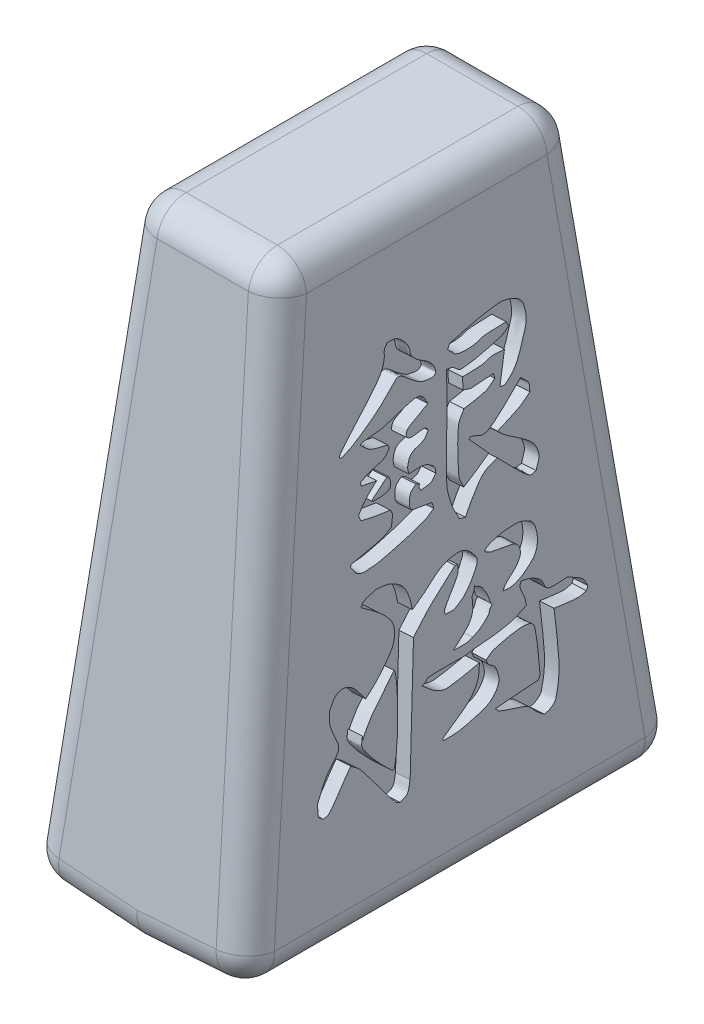
SolidWorks part; units mm, degrees
ref_plane "Płaszczyzna przednia" through (0, 0, 0) normal (0, 0, 1) x (1, 0, 0)
ref_plane "Płaszczyzna górna" through (0, 0, 0) normal (0, 1, 0) x (1, 0, 0)
ref_plane "Płaszczyzna prawa" through (0, 0, 0) normal (1, 0, 0) x (0, 0, -1)
sketch "Szkic1" plane through (0, 0, 0) normal (0, 0, 1) x (1, 0, 0)
  line L0 (0, 0) -> (0, 40)
  line L1 (3.1225, 40) -> (-3.1225, 40)
  line L2 (-5.1185, 38.1262) -> (-7.3738, 2.4704)
  line L3 (-5.504, 0.3481) -> (0, 0)
  line L4 (5.504, 0.3481) -> (0, 0)
  line L5 (5.1185, 38.1262) -> (7.3738, 2.4704)
  arc A0 (-3.1225, 40) -> (-5.1185, 38.1262) centre (-3.1225, 38) ccw
  arc A1 (-7.3738, 2.4704) -> (-5.504, 0.3481) centre (-5.3777, 2.3441) ccw
  arc A2 (7.3738, 2.4704) -> (5.504, 0.3481) centre (5.3777, 2.3441) cw
  arc A3 (3.1225, 40) -> (5.1185, 38.1262) centre (3.1225, 38) cw
  point P7 (-5, 40)
  point P10 (-7.5, 0.4744)
  point P17 (7.5, 0.4744)
  point P18 (5, 40)
  dimension "D5" = 2
  dimension "D1" = 40
  dimension "D2" = 90
  dimension "D3" = 5
  dimension "D4" = 7.5
extrude "Dodanie-wyciągnięcie1" add sketch "Szkic1" along normal blind 30 contours L2 A1 L3 L0 L1 A0 | A3 L1 L0 L4 A2 L5 region at (-3.1441, 18.7866, 0) region at (3.1441, 18.7866, 0)
ref_plane "Płaszczyzna1" through (5.1225, 0, 0) normal (1, 0, 0) x (0, 0, -1)
ref_plane "Płaszczyzna2" through (15.1225, 0, 0) normal (1, 0, 0) x (0, 0, -1)
sketch "Szkic7" plane through (15.1225, 0, 0) normal (1, 0, 0) x (0, 0, -1)
  line L0 (-25, 40) -> (-5, 40)
  line L1 (-30, 40) -> (0, 40) construction
  line L2 (-5, 40) -> (0, 0)
  line L3 (0, 0) -> (-30, 0)
  line L4 (-30, 0) -> (0, 0) construction
  line L5 (-15, 0) -> (-15, 40)
  line L6 (-25, 40) -> (-30, 0)
  line L8 (0, 0) -> (-30, 0)
  line L9 (0, 0) -> (0, 40)
  line L10 (0, 40) -> (-30, 40)
  line L11 (-30, 0) -> (-30, 40)
  dimension "D1" = 10
  dimension "D2" = 15
  dimension "D3" = 40
extrude "Wytnij-wyciągnięcie11" cut sketch "Szkic7" against normal through all and the other way through all contours L11 L6 L10 | L9 L10 L2 region at (15.1225, 26.6667, 28.3333) region at (15.1225, 26.6667, 1.6667)
fillet "Zaokrąglenie2" radius 2 18 edges at (0, 40, 5) (-4.4914, 39.4582, 4.9323) (-6.2461, 20.2983, 2.5373) (-6.8784, 1.022, 0.1278) (-2.752, 0.1741, 0.0218) (2.752, 0.1741, 0.0218) (6.8784, 1.022, 0.1278) (6.2461, 20.2983, 2.5373) (4.4914, 39.4582, 4.9323) (4.4914, 39.4582, 25.0677) (6.2461, 20.2983, 27.4627) (6.8784, 1.022, 29.8722) (2.752, 0.1741, 29.9782) (-2.752, 0.1741, 29.9782) (-6.8784, 1.022, 29.8722) (-6.2461, 20.2983, 27.4627) (-4.4914, 39.4582, 25.0677) (0, 40, 25)
sketch "Szkic8" plane through (7.5, 0.4744, 0) normal (0.998, 0.0631, 0) x (0, 0, -1)
  line L0 (200, 714.5) -> (1000, 714.5) construction
  line L1 (-16.3932, 23.4436) -> (-16.6352, 23.5536)
  line L2 (-17.0092, 22.2336) -> (-15.6452, 22.0136)
  line L3 (-15.6452, 22.0136) -> (-15.5352, 21.6176)
  line L4 (-21.2772, 21.0236) -> (-21.2112, 21.1556)
  line L5 (-19.2312, 25.0056) -> (-20.2872, 25.2036)
  line L6 (-20.2872, 25.2036) -> (-20.3092, 25.4236)
  line L7 (-18.2852, 26.4136) -> (-18.3732, 26.6556)
  line L8 (-18.5492, 24.8736) -> (-18.4392, 24.8516)
  line L9 (-19.6492, 24.0376) -> (-18.5492, 24.8736)
  line L10 (-10.7172, 26.2816) -> (-10.2772, 28.2396)
  line L11 (-13.1592, 28.0416) -> (-13.1812, 27.2936)
  line L12 (-11.0912, 27.2276) -> (-11.0252, 26.9196)
  line L13 (-11.6852, 22.9376) -> (-12.9612, 24.3456)
  line L14 (-13.4672, 20.0996) -> (-13.8632, 20.2096)
  line L15 (-9.9252, 29.3836) -> (-10.0572, 29.7136)
  line L16 (-14.1272, 17.7016) -> (-14.3252, 17.7456)
  line L17 (-17.3392, 15.0616) -> (-18.0652, 7.2076)
  line L18 (-23.9612, 7.8016) -> (-24.2912, 8.0656)
  line L19 (-12.3012, 17.5256) -> (-12.2792, 17.6796)
  line L20 (-5.5692, 12.3336) -> (-5.6792, 12.0916)
  line L21 (-12.1692, 8.4396) -> (-9.1992, 8.6596)
  spline S0 degree 3 poles (-20.1992, 27.5136) (-20.1552, 27.5429) (-20.1195, 27.5935) (-20.0672, 27.6016) (-19.5935, 27.675) (-19.1134, 27.6996) (-18.6372, 27.7556) (-18.6142, 27.7583) (-18.5935, 27.7712) (-18.5712, 27.7776) (-17.8749, 27.9766) (-17.1936, 28.241) (-16.4812, 28.3716) (-16.2973, 28.4053) (-16.08, 28.3749) (-15.9312, 28.2616) (-15.7451, 28.1198) (-15.6819, 27.8656) (-15.5572, 27.6676) knots 0 0 0 0 1 1 1 2 2 2 3 3 3 4 4 4 5 5 5 6 6 6 6
  spline S1 degree 3 poles (-15.5572, 27.6676) (-15.7626, 27.5576) (-15.9681, 27.448) (-16.1732, 27.3376) (-16.4448, 27.1914) (-16.7538, 27.0992) (-16.9872, 26.8976) (-17.0944, 26.805) (-17.0899, 26.6336) (-17.1412, 26.5016) knots 0 0 0 0 1 1 1 2 2 2 3 3 3 3
  spline S2 degree 3 poles (-17.1412, 26.5016) (-17.0386, 26.4429) (-16.9511, 26.3356) (-16.8332, 26.3256) (-16.5037, 26.2977) (-16.1713, 26.4334) (-15.8432, 26.3916) (-15.7404, 26.3785) (-15.6966, 26.2449) (-15.6232, 26.1716) knots 0 0 0 0 1 1 1 2 2 2 3 3 3 3
  spline S3 degree 3 poles (-15.6232, 26.1716) (-15.7332, 26.0396) (-15.8083, 25.8678) (-15.9532, 25.7756) (-16.2221, 25.6045) (-16.588, 25.6052) (-16.8332, 25.4016) (-17.0023, 25.2612) (-17.0702, 25.0218) (-17.1192, 24.8076) (-17.1538, 24.6568) (-17.0899, 24.4996) (-17.0752, 24.3456) knots 0 0 0 0 1 1 1 2 2 2 3 3 3 4 4 4 4
  spline S4 degree 3 poles (-17.0752, 24.3456) (-16.7232, 24.3456) (-16.3612, 24.4289) (-16.0192, 24.3456) (-15.7662, 24.284) (-15.5329, 24.1217) (-15.3592, 23.9276) (-15.2643, 23.8215) (-15.3006, 23.6489) (-15.2712, 23.5096) knots 0 0 0 0 1 1 1 2 2 2 3 3 3 3
  spline S5 degree 3 poles (-15.2712, 23.5096) (-15.3959, 23.3923) (-15.4879, 23.225) (-15.6452, 23.1576) (-15.8636, 23.064) (-16.1146, 23.0843) (-16.3492, 23.0476) knots 0 0 0 0 1 1 1 2 2 2 2
  spline S6 degree 3 poles (-16.3492, 23.0476) (-16.3786, 23.1356) (-16.427, 23.2194) (-16.4372, 23.3116) (-16.4424, 23.3577) (-16.4079, 23.3996) (-16.3932, 23.4436) knots 0 0 0 0 1 1 1 2 2 2 2
  spline S7 degree 3 poles (-16.6352, 23.5536) (-16.7672, 23.4363) (-16.9523, 23.3596) (-17.0312, 23.2016) (-17.131, 23.0021) (-17.1463, 22.7646) (-17.1412, 22.5416) (-17.1387, 22.4299) (-17.0532, 22.3363) (-17.0092, 22.2336) knots 0 0 0 0 1 1 1 2 2 2 3 3 3 3
  spline S8 degree 3 poles (-15.5352, 21.6176) (-15.7552, 21.4929) (-15.9561, 21.3257) (-16.1952, 21.2436) (-16.988, 20.9716) (-17.7946, 20.7319) (-18.6152, 20.5616) (-18.9814, 20.4856) (-19.3426, 20.3723) (-19.7152, 20.3416) (-20.0591, 20.3132) (-20.4331, 20.2476) (-20.7492, 20.3856) (-21.0022, 20.4961) (-21.1012, 20.8109) (-21.2772, 21.0236) knots 0 0 0 0 1 1 1 2 2 2 3 3 3 4 4 4 5 5 5 5
  spline S9 degree 3 poles (-21.2112, 21.1556) (-20.4926, 21.3096) (-19.7624, 21.4172) (-19.0552, 21.6176) (-18.8249, 21.6829) (-18.6299, 21.8376) (-18.4172, 21.9476) knots 0 0 0 0 1 1 1 2 2 2 2
  spline S10 degree 3 poles (-18.4172, 21.9476) (-18.3806, 22.1676) (-18.3072, 22.3846) (-18.3072, 22.6076) (-18.3072, 22.7166) (-18.3806, 22.8129) (-18.4172, 22.9156) knots 0 0 0 0 1 1 1 2 2 2 2
  spline S11 degree 3 poles (-18.4172, 22.9156) (-18.8132, 22.9743) (-19.211, 23.0223) (-19.6052, 23.0916) (-19.8787, 23.1397) (-20.1479, 23.2089) (-20.4192, 23.2676) knots 0 0 0 0 1 1 1 2 2 2 2
  spline S12 degree 3 poles (-20.4192, 23.2676) (-20.4632, 23.3849) (-20.5194, 23.4984) (-20.5512, 23.6196) (-20.5571, 23.642) (-20.5433, 23.6672) (-20.5292, 23.6856) (-20.3518, 23.9176) (-20.184, 24.1594) (-19.9792, 24.3676) (-19.7495, 24.6013) (-19.4806, 24.7929) (-19.2312, 25.0056) knots 0 0 0 0 1 1 1 2 2 2 3 3 3 4 4 4 4
  spline S13 degree 3 poles (-20.3092, 25.4236) (-20.1259, 25.5116) (-19.9506, 25.6187) (-19.7592, 25.6876) (-19.3991, 25.8173) (-19.0027, 25.8485) (-18.6592, 26.0176) (-18.4964, 26.0978) (-18.4099, 26.2816) (-18.2852, 26.4136) knots 0 0 0 0 1 1 1 2 2 2 3 3 3 3
  spline S14 degree 3 poles (-18.3732, 26.6556) (-18.7619, 26.7583) (-19.1754, 26.7926) (-19.5392, 26.9636) (-19.7984, 27.0854) (-19.9792, 27.3303) (-20.1992, 27.5136) knots 0 0 0 0 1 1 1 2 2 2 2
  spline S15 degree 3 poles (-18.4392, 24.8516) (-18.4099, 24.7929) (-18.3685, 24.7389) (-18.3512, 24.6756) (-18.2147, 24.175) (-18.4063, 24.0688) (-18.8572, 23.9936) (-18.9012, 23.9863) (-18.9446, 23.9716) (-18.9892, 23.9716) (-19.9184, 23.9716) (-19.3428, 23.9355) (-19.6492, 24.0376) knots 0 0 0 0 1 1 1 2 2 2 3 3 3 4 4 4 4
  spline S16 degree 3 poles (-16.6132, 29.5596) (-16.8166, 29.7141) (-16.9855, 29.9169) (-17.2072, 30.0436) (-17.3157, 30.1056) (-17.487, 30.1475) (-17.5812, 30.0656) (-18.0166, 29.6873) (-18.4204, 29.271) (-18.8792, 28.9216) (-19.376, 28.5433) (-19.9041, 28.2061) (-20.4412, 27.8876) (-20.7347, 27.7136) (-21.0441, 27.5627) (-21.3652, 27.4476) (-21.4415, 27.4203) (-21.5876, 27.391) (-21.6072, 27.4696) (-21.6367, 27.5874) (-21.5351, 27.71) (-21.4532, 27.7996) (-20.6803, 28.6458) (-19.8302, 29.4192) (-19.0552, 30.2636) (-18.846, 30.4916) (-18.6598, 30.7435) (-18.5052, 31.0116) (-18.408, 31.1804) (-18.3545, 31.3726) (-18.3072, 31.5616) (-18.2549, 31.771) (-18.3321, 32.0311) (-18.1972, 32.1996) (-18.1485, 32.2605) (-18.0946, 32.3169) (-18.0432, 32.3756) knots 13 13 13 13 14 14 14 15 15 15 16 16 16 17 17 17 18 18 18 19 19 19 20 20 20 21 21 21 22 22 22 23 23 23 24 24 24 25 25 25 25
  spline S17 degree 3 poles (-18.0432, 32.3756) (-17.8526, 32.3609) (-17.6448, 32.4119) (-17.4712, 32.3316) (-17.2301, 32.22) (-17.0338, 32.0224) (-16.8552, 31.8256) (-16.7428, 31.7016) (-16.6728, 31.542) (-16.6132, 31.3856) (-16.5543, 31.231) (-16.5853, 31.0452) (-16.5032, 30.9016) (-16.4029, 30.726) (-16.2426, 30.5887) (-16.0852, 30.4616) (-15.859, 30.2788) (-15.5801, 30.1669) (-15.3592, 29.9776) (-15.2166, 29.8554) (-15.0966, 29.7028) (-15.0072, 29.5376) (-14.9463, 29.4249) (-14.9392, 29.2901) (-14.9192, 29.1636) (-14.9167, 29.1474) (-14.928, 29.1292) (-14.9412, 29.1196) (-15.0104, 29.0693) (-15.0758, 28.9918) (-15.1612, 28.9876) (-15.3902, 28.9764) (-15.62, 29.0237) (-15.8432, 29.0756) (-15.9391, 29.0979) (-16.0239, 29.1552) (-16.1072, 29.2076) (-16.2812, 29.3169) (-16.4497, 29.4353) (-16.6132, 29.5596) knots 0 0 0 0 1 1 1 2 2 2 3 3 3 4 4 4 5 5 5 6 6 6 7 7 7 8 8 8 9 9 9 10 10 10 11 11 11 12 12 12 13 13 13 13
  spline S18 degree 3 poles (-14.0612, 30.0436) (-13.9879, 30.1389) (-13.9573, 30.298) (-13.8412, 30.3296) (-12.7727, 30.6204) (-11.6877, 30.8854) (-10.5852, 30.9896) (-10.1901, 31.027) (-9.7779, 30.9177) (-9.4192, 30.7476) (-9.1803, 30.6342) (-8.952, 30.4268) (-8.8692, 30.1756) (-8.7246, 29.7366) (-8.6508, 29.2177) (-8.8252, 28.7896) (-9.056, 28.2233) (-9.2146, 27.6199) (-9.5292, 27.0956) (-9.7294, 26.7621) (-10.0224, 26.4794) (-10.3432, 26.2596) (-10.4463, 26.189) (-10.5926, 26.2743) (-10.7172, 26.2816) knots 0 0 0 0 1 1 1 2 2 2 3 3 3 4 4 4 5 5 5 6 6 6 7 7 7 8 8 8 8
  spline S19 degree 3 poles (-10.2772, 28.2396) (-10.5706, 28.2469) (-10.8652, 28.29) (-11.1572, 28.2616) (-11.398, 28.2382) (-11.6208, 28.112) (-11.8612, 28.0856) (-12.2916, 28.0383) (-12.7266, 28.0563) (-13.1592, 28.0416) knots 0 0 0 0 1 1 1 2 2 2 3 3 3 3
  spline S20 degree 3 poles (-13.1812, 27.2936) (-12.9906, 27.2349) (-12.8035, 27.1629) (-12.6092, 27.1176) (-12.5798, 27.1107) (-12.5514, 27.1374) (-12.5212, 27.1396) (-12.0449, 27.1741) (-11.5679, 27.1983) (-11.0912, 27.2276) knots 0 0 0 0 1 1 1 2 2 2 3 3 3 3
  spline S21 degree 3 poles (-11.0252, 26.9196) (-11.2452, 26.7803) (-11.4377, 26.5824) (-11.6852, 26.5016) (-12.1679, 26.344) (-12.6826, 26.3109) (-13.1812, 26.2156) knots 0 0 0 0 1 1 1 2 2 2 2
  spline S22 degree 3 poles (-13.1812, 26.2156) (-13.3206, 25.9663) (-13.5545, 25.7497) (-13.5992, 25.4676) (-13.7487, 24.5247) (-13.7879, 23.5617) (-13.7532, 22.6076) (-13.7433, 22.334) (-13.5626, 22.0943) (-13.4672, 21.8376) knots 0 0 0 0 1 1 1 2 2 2 3 3 3 3
  spline S23 degree 3 poles (-13.4672, 21.8376) (-12.8678, 22.1953) (-12.2614, 22.5434) (-11.6852, 22.9376) knots 0 0 0 0 1 1 1 1
  spline S24 degree 3 poles (-12.9612, 24.3456) (-12.9099, 24.3749) (-12.8656, 24.4433) (-12.8072, 24.4336) (-12.4982, 24.3821) (-12.2135, 24.1136) (-11.9052, 24.1696) (-11.5105, 24.2414) (-11.1915, 24.544) (-10.8712, 24.7856) (-10.3232, 25.1989) (-9.8299, 25.6803) (-9.3092, 26.1276) knots 0 0 0 0 1 1 1 2 2 2 3 3 3 4 4 4 4
  spline S25 degree 3 poles (-9.3092, 26.1276) (-9.1406, 25.9516) (-8.9157, 25.8159) (-8.8032, 25.5996) (-8.7147, 25.4293) (-8.7592, 25.2183) (-8.7372, 25.0276) knots 0 0 0 0 1 1 1 2 2 2 2
  spline S26 degree 3 poles (-8.7372, 25.0276) (-9.0012, 24.8516) (-9.2455, 24.6415) (-9.5292, 24.4996) (-10.0116, 24.2584) (-10.5266, 24.0889) (-11.0252, 23.8836) knots 0 0 0 0 1 1 1 2 2 2 2
  spline S27 degree 3 poles (-11.0252, 23.8836) (-10.9006, 23.7589) (-10.7908, 23.6174) (-10.6512, 23.5096) (-10.0487, 23.0443) (-9.3468, 22.7007) (-8.8032, 22.1676) (-8.5644, 21.9334) (-8.4011, 21.598) (-8.3632, 21.2656) (-8.3304, 20.9774) (-8.5246, 20.7083) (-8.6052, 20.4296) knots 0 0 0 0 1 1 1 2 2 2 3 3 3 4 4 4 4
  spline S28 degree 3 poles (-8.6052, 20.4296) (-8.7519, 20.4149) (-8.918, 20.3112) (-9.0452, 20.3856) (-9.4264, 20.6084) (-9.7164, 20.9602) (-10.0352, 21.2656) (-10.4135, 21.6279) (-10.7686, 22.0136) (-11.1352, 22.3876) knots 0 0 0 0 1 1 1 2 2 2 3 3 3 3
  spline S29 degree 3 poles (-11.1352, 22.3876) (-11.4506, 22.2556) (-11.813, 22.2035) (-12.0812, 21.9916) (-12.4246, 21.7203) (-12.6587, 21.3326) (-12.9172, 20.9796) (-13.1217, 20.7006) (-13.2839, 20.3929) (-13.4672, 20.0996) knots 0 0 0 0 1 1 1 2 2 2 3 3 3 3
  spline S30 degree 3 poles (-13.8632, 20.2096) (-14.0172, 20.5396) (-14.2179, 20.8516) (-14.3252, 21.1996) (-14.4617, 21.6421) (-14.5942, 22.1005) (-14.5892, 22.5636) (-14.5721, 24.1586) (-14.3523, 25.7452) (-14.2592, 27.3376) (-14.2276, 27.8795) (-14.2299, 28.4229) (-14.2152, 28.9656) knots 0 0 0 0 1 1 1 2 2 2 3 3 3 4 4 4 4
  spline S31 degree 3 poles (-14.2152, 28.9656) (-14.0832, 28.9436) (-13.942, 28.953) (-13.8192, 28.8996) (-13.5989, 28.8038) (-13.4433, 28.5159) (-13.2032, 28.5256) (-12.308, 28.5619) (-11.4301, 28.8047) (-10.5632, 29.0316) (-10.3283, 29.0931) (-10.1379, 29.2663) (-9.9252, 29.3836) knots 0 0 0 0 1 1 1 2 2 2 3 3 3 4 4 4 4
  spline S32 degree 3 poles (-10.0572, 29.7136) (-10.5706, 29.6916) (-11.0867, 29.7054) (-11.5972, 29.6476) (-11.8676, 29.617) (-12.1178, 29.4688) (-12.3892, 29.4496) (-12.7484, 29.4242) (-13.128, 29.3951) (-13.4672, 29.5156) (-13.7169, 29.6043) (-13.8632, 29.8676) (-14.0612, 30.0436) knots 0 0 0 0 1 1 1 2 2 2 3 3 3 4 4 4 4
  spline S33 degree 3 poles (-20.7272, 18.4276) (-20.6612, 18.5083) (-20.6216, 18.6213) (-20.5292, 18.6696) (-20.2888, 18.7953) (-20.0152, 18.8437) (-19.7592, 18.9336) (-19.7438, 18.939) (-19.7315, 18.9574) (-19.7152, 18.9556) (-19.3988, 18.9204) (-19.0675, 18.935) (-18.7692, 18.8236) (-18.4452, 18.7026) (-18.1297, 18.5223) (-17.8892, 18.2736) (-17.6886, 18.0661) (-17.5889, 17.7759) (-17.4932, 17.5036) (-17.3965, 17.2282) (-17.3759, 16.9316) (-17.3172, 16.6456) knots 0 0 0 0 1 1 1 2 2 2 3 3 3 4 4 4 5 5 5 6 6 6 7 7 7 7
  spline S34 degree 3 poles (-17.3172, 16.6456) (-17.0606, 16.8143) (-16.7985, 16.9749) (-16.5472, 17.1516) (-16.1309, 17.4444) (-15.7632, 17.812) (-15.3152, 18.0536) (-15.0049, 18.221) (-14.6536, 18.3217) (-14.3032, 18.3616) (-14.0601, 18.3893) (-13.7871, 18.3775) (-13.5772, 18.2516) (-13.2836, 18.0754) (-13.0349, 17.8054) (-12.8732, 17.5036) (-12.7967, 17.3608) (-12.8448, 17.1645) (-12.9172, 17.0196) (-13.1155, 16.623) (-13.3603, 16.2415) (-13.6652, 15.9196) (-13.8975, 15.6745) (-14.1881, 15.4738) (-14.5012, 15.3476) (-14.6986, 15.2681) (-14.9266, 15.3329) (-15.1392, 15.3256) knots 0 0 0 0 1 1 1 2 2 2 3 3 3 4 4 4 5 5 5 6 6 6 7 7 7 8 8 8 9 9 9 9
  spline S35 degree 3 poles (-15.1392, 15.3256) (-15.1539, 15.4136) (-15.2243, 15.5104) (-15.1832, 15.5896) (-14.8997, 16.1369) (-14.4689, 16.6002) (-14.1932, 17.1516) (-14.1107, 17.3168) (-14.1492, 17.5183) (-14.1272, 17.7016) knots 0 0 0 0 1 1 1 2 2 2 3 3 3 3
  spline S36 degree 3 poles (-14.3252, 17.7456) (-14.9192, 17.2616) (-15.535, 16.8032) (-16.1072, 16.2936) (-16.541, 15.9074) (-16.9286, 15.4723) (-17.3392, 15.0616) knots 0 0 0 0 1 1 1 2 2 2 2
  spline S37 degree 3 poles (-18.0652, 7.2076) (-18.0726, 7.1856) (-18.0795, 7.1635) (-18.0872, 7.1416) (-18.1602, 6.9361) (-18.1664, 6.692) (-18.3072, 6.5256) (-18.428, 6.3829) (-18.6446, 6.3643) (-18.8132, 6.2836) knots 0 0 0 0 1 1 1 2 2 2 3 3 3 3
  spline S38 degree 3 poles (-18.8132, 6.2836) (-18.9159, 6.3349) (-19.0488, 6.3485) (-19.1212, 6.4376) (-19.8845, 7.3765) (-20.5311, 8.4067) (-21.2992, 9.3416) (-21.481, 9.5629) (-21.7392, 9.7083) (-21.9592, 9.8916) knots 0 0 0 0 1 1 1 2 2 2 3 3 3 3
  spline S39 degree 3 poles (-21.9592, 9.8916) (-22.0766, 9.7523) (-22.1959, 9.6146) (-22.3112, 9.4736) (-22.7239, 8.9692) (-23.0855, 8.4194) (-23.5432, 7.9556) (-23.6475, 7.8499) (-23.8219, 7.8529) (-23.9612, 7.8016) knots 0 0 0 0 1 1 1 2 2 2 3 3 3 3
  spline S40 degree 3 poles (-24.2912, 8.0656) (-24.2986, 8.3003) (-24.3194, 8.5349) (-24.3132, 8.7696) (-24.312, 8.816) (-24.2906, 8.8604) (-24.2692, 8.9016) (-24.0703, 9.2863) (-23.8994, 9.6892) (-23.6532, 10.0456) (-23.4051, 10.4049) (-23.0362, 10.6714) (-22.7952, 11.0356) (-22.7127, 11.1603) (-22.6744, 11.3297) (-22.7072, 11.4756) (-22.8101, 11.9328) (-23.093, 12.3374) (-23.1912, 12.7956) (-23.2497, 13.0682) (-23.1828, 13.3532) (-23.1692, 13.6316) (-23.1681, 13.6548) (-23.1601, 13.6783) (-23.1472, 13.6976) (-23.0129, 13.899) (-22.917, 14.1388) (-22.7292, 14.2916) (-22.5854, 14.4087) (-22.3862, 14.4816) (-22.2012, 14.4676) (-21.9717, 14.4503) (-21.736, 14.3557) (-21.5632, 14.2036) (-21.2306, 13.9107) (-21.0059, 13.5143) (-20.7272, 13.1696) knots 0 0 0 0 1 1 1 2 2 2 3 3 3 4 4 4 5 5 5 6 6 6 7 7 7 8 8 8 9 9 9 10 10 10 11 11 11 12 12 12 12
  spline S41 degree 3 poles (-20.7272, 13.1696) (-20.4339, 13.4189) (-20.1163, 13.6423) (-19.8472, 13.9176) (-19.4837, 14.2896) (-19.1127, 14.6655) (-18.8352, 15.1056) (-18.6794, 15.3528) (-18.5875, 15.6498) (-18.5712, 15.9416) (-18.557, 16.1973) (-18.6159, 16.4697) (-18.7472, 16.6896) (-18.9415, 17.0149) (-19.2325, 17.2757) (-19.5172, 17.5256) (-19.8953, 17.8575) (-20.3239, 18.1269) (-20.7272, 18.4276) knots 0 0 0 0 1 1 1 2 2 2 3 3 3 4 4 4 5 5 5 6 6 6 6
  spline S42 degree 3 poles (-18.9232, 9.0116) (-18.9671, 8.8071) (-18.9665, 8.7287) (-19.0112, 8.5496) (-19.0138, 8.5395) (-19.0296, 8.5373) (-19.0332, 8.5276) (-19.1035, 8.3402) (-19.0349, 8.4159) (-19.0992, 8.3516) (-19.1139, 8.3369) (-19.1225, 8.3076) (-19.1432, 8.3076) (-19.2303, 8.3076) (-19.2475, 8.3508) (-19.2972, 8.3956) (-19.3552, 8.4477) (-19.4171, 8.4955) (-19.4732, 8.5496) (-19.7161, 8.7834) (-19.95, 9.0267) (-20.1772, 9.2756) (-20.4413, 9.5648) (-20.7073, 9.8727) (-20.9252, 10.1996) (-21.009, 10.3252) (-21.1008, 10.4513) (-21.1452, 10.5956) (-21.1584, 10.6382) (-21.175, 10.6837) (-21.1672, 10.7276) (-20.9918, 11.7218) (-21.1501, 10.8192) (-21.0572, 10.9916) (-20.9633, 11.1661) (-20.8821, 11.3374) (-20.7712, 11.4976) (-20.6716, 11.6415) (-20.5852, 11.7757) (-20.4852, 11.9156) (-20.3457, 12.111) (-20.1619, 12.2889) (-20.0012, 12.4656) (-19.5822, 12.9265) (-19.1574, 13.3828) (-18.7472, 13.8516) knots 15 15 15 15 16 16 16 17 17 17 18 18 18 19 19 19 20 20 20 21 21 21 22 22 22 23 23 23 24 24 24 25 25 25 26 26 26 27 27 27 28 28 28 29 29 29 30 30 30 30
  spline S43 degree 3 poles (-18.7472, 13.8516) (-18.7326, 13.8369) (-18.7089, 13.8275) (-18.7032, 13.8076) (-18.6787, 13.7218) (-18.6671, 13.6325) (-18.6592, 13.5436) (-18.6378, 13.3021) (-18.6179, 13.06) (-18.6152, 12.8176) (-18.6106, 12.3996) (-18.6228, 11.9814) (-18.6372, 11.5636) (-18.6376, 11.5532) (-18.6585, 11.5519) (-18.6592, 11.5416) (-18.6807, 11.2487) (-18.6818, 10.9545) (-18.7032, 10.6616) (-18.704, 10.6513) (-18.7243, 10.6499) (-18.7252, 10.6396) (-18.7465, 10.4128) (-18.748, 10.1844) (-18.7692, 9.9576) (-18.7702, 9.9473) (-18.79, 9.9459) (-18.7912, 9.9356) (-18.8049, 9.8262) (-18.7996, 9.715) (-18.8132, 9.6056) (-18.8145, 9.5953) (-18.8338, 9.5939) (-18.8352, 9.5836) (-18.8488, 9.4889) (-18.8437, 9.3923) (-18.8572, 9.2976) (-18.8587, 9.2873) (-18.8775, 9.2858) (-18.8792, 9.2756) (-18.8926, 9.1957) (-18.8879, 9.1135) (-18.9012, 9.0336) (-18.9029, 9.0234) (-18.9211, 9.0217) (-18.9232, 9.0116) knots 0 0 0 0 1 1 1 2 2 2 3 3 3 4 4 4 5 5 5 6 6 6 7 7 7 8 8 8 9 9 9 10 10 10 11 11 11 12 12 12 13 13 13 14 14 14 15 15 15 15
  spline S44 degree 3 poles (-13.4012, 13.1696) (-13.5474, 13.1165) (-13.7818, 13.0376) (-13.9512, 13.0376) (-14.208, 13.0376) (-14.4677, 13.0187) (-14.7212, 13.0596) (-14.7622, 13.0662) (-14.6645, 13.1203) (-14.6332, 13.1476) (-14.5703, 13.2027) (-14.5005, 13.2494) (-14.4352, 13.3016) (-14.1804, 13.5055) (-13.9093, 13.6991) (-13.6872, 13.9396) (-13.4559, 14.1902) (-13.2912, 14.5402) (-13.2912, 14.8856) (-13.2912, 14.896) (-13.3132, 14.8972) (-13.3132, 14.9076) (-13.3132, 15.0984) (-13.3053, 15.2893) (-13.2912, 15.4796) (-13.2904, 15.4911) (-13.2361, 15.5707) (-13.2252, 15.5896) (-13.2008, 15.6323) (-13.1724, 15.6742) (-13.1592, 15.7216) (-13.1354, 15.8076) (-13.1299, 15.8976) (-13.1152, 15.9856) knots 12 12 12 12 13 13 13 14 14 14 15 15 15 16 16 16 17 17 17 18 18 18 19 19 19 20 20 20 21 21 21 22 22 22 23 23 23 23
  spline S45 degree 3 poles (-13.1152, 15.9856) (-13.1006, 15.9783) (-13.0828, 15.9752) (-13.0712, 15.9636) (-13.0453, 15.9377) (-13.0374, 15.8932) (-13.0052, 15.8756) (-12.9522, 15.8466) (-12.8866, 15.8507) (-12.8292, 15.8316) (-12.8194, 15.8283) (-12.8157, 15.8156) (-12.8072, 15.8096) (-12.6691, 15.711) (-12.636, 15.6847) (-12.5432, 15.5456) (-12.3666, 15.2806) (-12.2323, 14.9938) (-12.1472, 14.6876) (-12.1311, 14.6293) (-12.1257, 14.5677) (-12.1032, 14.5116) (-12.0955, 14.4923) (-12.0707, 14.4849) (-12.0592, 14.4676) (-12.0411, 14.4403) (-12.004, 14.4104) (-12.0152, 14.3796) (-12.0383, 14.3161) (-12.1141, 14.2845) (-12.1472, 14.2256) (-12.1862, 14.1564) (-12.2113, 13.9898) (-12.2792, 13.9176) (-12.5959, 13.5812) (-12.9679, 13.3272) (-13.4012, 13.1696) knots 0 0 0 0 1 1 1 2 2 2 3 3 3 4 4 4 5 5 5 6 6 6 7 7 7 8 8 8 9 9 9 10 10 10 11 11 11 12 12 12 12
  spline S46 degree 3 poles (-12.2792, 17.6796) (-12.1179, 17.7529) (-11.9659, 17.8519) (-11.7952, 17.8996) (-11.4642, 17.9921) (-11.1265, 18.0803) (-10.7832, 18.0976) (-10.2157, 18.1263) (-9.94, 18.179) (-9.5732, 17.9876) (-9.4191, 17.9072) (-9.236, 17.8666) (-9.1112, 17.7456) (-8.9839, 17.6221) (-8.8985, 17.4534) (-8.8472, 17.2836) (-8.7789, 17.0572) (-8.7514, 16.816) (-8.7592, 16.5796) (-8.7662, 16.3697) (-8.8071, 16.156) (-8.8912, 15.9636) (-8.9647, 15.7956) (-9.083, 15.644) (-9.2212, 15.5236) (-9.4836, 15.2952) (-9.7718, 15.0924) (-10.0792, 14.9296) (-10.276, 14.8254) (-10.4966, 14.7613) (-10.7172, 14.7316) (-10.885, 14.709) (-11.0546, 14.7609) (-11.2232, 14.7756) knots 0 0 0 0 1 1 1 2 2 2 3 3 3 4 4 4 5 5 5 6 6 6 7 7 7 8 8 8 9 9 9 10 10 10 11 11 11 11
  spline S47 degree 3 poles (-11.2232, 14.7756) (-11.1719, 14.8636) (-11.1413, 14.9676) (-11.0692, 15.0396) (-10.8302, 15.2786) (-10.5312, 15.4537) (-10.2992, 15.6996) (-10.1611, 15.8461) (-10.0279, 16.013) (-9.9692, 16.2056) (-9.9201, 16.3671) (-9.9315, 16.5537) (-9.9912, 16.7116) (-10.0408, 16.8426) (-10.1508, 16.9593) (-10.2772, 17.0196) (-10.4876, 17.12) (-10.7307, 17.1279) (-10.9592, 17.1736) (-11.2808, 17.2379) (-11.6054, 17.2866) (-11.9272, 17.3496) (-11.9433, 17.3527) (-11.9564, 17.3646) (-11.9712, 17.3716) (-12.0811, 17.4233) (-12.1912, 17.4743) (-12.3012, 17.5256) knots 0 0 0 0 1 1 1 2 2 2 3 3 3 4 4 4 5 5 5 6 6 6 7 7 7 8 8 8 9 9 9 9
  spline S48 degree 3 poles (-9.7272, 13.2136) (-9.7566, 13.3823) (-9.7666, 13.5555) (-9.8152, 13.7196) (-9.8845, 13.9533) (-10.0252, 14.1639) (-10.0792, 14.4016) (-10.1006, 14.4957) (-10.0657, 14.5961) (-10.0352, 14.6876) (-10.0269, 14.7127) (-9.9953, 14.7361) (-9.9692, 14.7316) (-9.7308, 14.6907) (-9.4866, 14.6531) (-9.2652, 14.5556) (-9.0475, 14.4596) (-8.8336, 14.3336) (-8.6712, 14.1596) (-8.5167, 13.994) (-8.5082, 13.7187) (-8.3412, 13.5656) (-8.2232, 13.4574) (-8.0391, 13.4436) (-7.8792, 13.4336) (-7.5642, 13.4139) (-7.2488, 13.4707) (-6.9332, 13.4776) (-6.9101, 13.4781) (-6.8874, 13.4672) (-6.8672, 13.4556) (-6.5423, 13.2689) (-6.1828, 13.1287) (-5.8992, 12.8836) (-5.7375, 12.7438) (-5.6792, 12.5169) (-5.5692, 12.3336) knots 0 0 0 0 1 1 1 2 2 2 3 3 3 4 4 4 5 5 5 6 6 6 7 7 7 8 8 8 9 9 9 10 10 10 11 11 11 12 12 12 12
  spline S49 degree 3 poles (-5.6792, 12.0916) (-5.8772, 12.0549) (-6.072, 11.9756) (-6.2732, 11.9816) (-6.8188, 11.9978) (-7.3586, 12.0989) (-7.9012, 12.1576) knots 0 0 0 0 1 1 1 2 2 2 2
  spline S50 degree 3 poles (-7.9012, 12.1576) (-7.8572, 11.0283) (-7.7254, 9.8989) (-7.7692, 8.7696) (-7.7918, 8.1876) (-7.9081, 7.6038) (-8.0992, 7.0536) (-8.1588, 6.8821) (-8.341, 6.7755) (-8.4952, 6.6796) (-8.6193, 6.6025) (-8.7739, 6.5916) (-8.9132, 6.5476) knots 0 0 0 0 1 1 1 2 2 2 3 3 3 4 4 4 4
  spline S51 degree 3 poles (-8.9132, 6.5476) (-9.0819, 6.6796) (-9.2599, 6.8005) (-9.4192, 6.9436) (-9.6199, 7.1238) (-9.7592, 7.3783) (-9.9912, 7.5156) (-10.2927, 7.6939) (-10.6509, 7.7512) (-10.9812, 7.8676) (-11.2962, 7.9786) (-11.6226, 8.0608) (-11.9272, 8.1976) (-11.9889, 8.2253) (-12.0114, 8.3038) (-12.0592, 8.3516) (-12.0924, 8.3848) (-12.1326, 8.4103) (-12.1692, 8.4396) knots 0 0 0 0 1 1 1 2 2 2 3 3 3 4 4 4 5 5 5 6 6 6 6
  spline S52 degree 3 poles (-9.1992, 8.6596) (-9.1552, 8.7476) (-9.0658, 8.8252) (-9.0672, 8.9236) (-9.0807, 9.8494) (-9.1087, 10.7796) (-9.2432, 11.6956) (-9.266, 11.8509) (-9.3831, 12.0123) (-9.5292, 12.0696) (-9.7895, 12.1717) (-10.0874, 12.1667) (-10.3652, 12.1356) (-10.9455, 12.0706) (-11.523, 11.9549) (-12.0812, 11.7836) (-12.2737, 11.7245) (-12.4186, 11.5636) (-12.5872, 11.4536) knots 0 0 0 0 1 1 1 2 2 2 3 3 3 4 4 4 5 5 5 6 6 6 6
  spline S53 degree 3 poles (-12.5872, 11.4536) (-12.5432, 11.3509) (-12.527, 11.2312) (-12.4552, 11.1456) (-12.3315, 10.9981) (-12.1038, 10.9425) (-12.0152, 10.7716) (-11.8803, 10.511) (-11.7911, 10.2059) (-11.8172, 9.9136) (-11.838, 9.6816) (-11.9918, 9.4711) (-12.1472, 9.2976) (-12.3156, 9.1097) (-12.527, 8.9462) (-12.7632, 8.8576) (-13.3595, 8.634) (-13.9842, 8.4843) (-14.6112, 8.3736) (-14.9871, 8.3073) (-15.3739, 8.3443) (-15.7552, 8.3296) knots 0 0 0 0 1 1 1 2 2 2 3 3 3 4 4 4 5 5 5 6 6 6 7 7 7 7
  spline S54 degree 3 poles (-15.7552, 8.3296) (-15.7406, 8.3809) (-15.7541, 8.4518) (-15.7112, 8.4836) (-15.1214, 8.9208) (-14.4448, 9.2402) (-13.8852, 9.7156) (-13.6058, 9.953) (-13.3794, 10.2629) (-13.2252, 10.5956) (-13.0934, 10.8801) (-13.1079, 11.2116) (-13.0492, 11.5196) knots 0 0 0 0 1 1 1 2 2 2 3 3 3 4 4 4 4
  spline S55 degree 3 poles (-13.0492, 11.5196) (-13.7899, 11.3949) (-14.5215, 11.1904) (-15.2712, 11.1456) (-15.5216, 11.1307) (-15.7782, 11.2213) (-15.9972, 11.3436) (-16.3533, 11.5424) (-16.6426, 11.8423) (-16.9652, 12.0916) knots 0 0 0 0 1 1 1 2 2 2 3 3 3 3
  spline S56 degree 3 poles (-16.9652, 12.0916) (-16.8919, 12.1136) (-16.8131, 12.1222) (-16.7452, 12.1576) (-16.6424, 12.2112) (-16.5748, 12.3464) (-16.4592, 12.3556) (-15.6331, 12.4212) (-14.8018, 12.3633) (-13.9732, 12.3776) (-13.9501, 12.378) (-13.9301, 12.396) (-13.9072, 12.3996) (-12.7046, 12.5903) (-11.4244, 12.506) (-10.2992, 12.9716) (-10.1079, 13.0508) (-9.9179, 13.1329) (-9.7272, 13.2136) knots 0 0 0 0 1 1 1 2 2 2 3 3 3 4 4 4 5 5 5 6 6 6 6
extrude "Wytnij-wyciągnięcie12" cut sketch "Szkic8" against normal blind 1 contours S14 L7 S13 L6 L5 S12 S11 S10 S9 L4 S8 L3 L2 S7 L1 S6 S5 S4 S3 S2 S1 S0 L8 S15 L9 | S17 S16 | S32 L15 S31 S30 L14 S29 S28 S27 S26 S25 S24 L13 S23 S22 S21 L12 S20 L11 S19 L10 S18 | S41 S40 L18 S39 S38 S37 L17 S36 L16 S35 S34 S33 S42 S43 | S45 S44 | S47 S46 L19 | S56 S55 S54 S53 S52 L21 S51 S50 S49 L20 S48 region at (5.9688, 24.6828, 18.0045) region at (5.7809, 27.6531, 10.3748) region at (6.3707, 18.3292, 14.1891) region at (6.3893, 18.0349, 12.2416) region at (6.7254, 12.7206, 5.752) region at (5.6055, 30.4267, 18.0934) region at (6.5955, 14.7751, 13.1171)
sketch "Szkic9" plane through (-7.5, 0.4744, 0) normal (-0.998, 0.0631, 0) x (0, 0, 1)
  line L0 (166.6667, 500) -> (833.3333, 500) construction
  line L1 (16.0383, 14.6927) -> (16.0883, 13.4927)
  line L2 (15.9883, 11.5927) -> (16.0383, 10.2427)
  line L3 (15.8883, 8.4927) -> (15.9383, 7.3427)
  line L4 (12.0883, 8.4927) -> (11.4383, 8.8427)
  line L5 (10.3383, 12.8927) -> (10.3883, 13.3427)
  line L6 (14.2383, 13.1927) -> (14.0883, 14.5427)
  line L7 (13.9383, 11.1927) -> (13.7883, 9.7427)
  line L8 (13.7883, 9.7427) -> (12.8383, 9.9427)
  line L9 (12.8383, 9.9427) -> (12.1383, 9.8927)
  line L10 (12.1383, 9.8927) -> (12.1383, 9.8427)
  line L11 (12.1383, 9.8427) -> (11.9383, 10.0427)
  line L12 (5.1883, 13.5427) -> (4.9383, 13.7927)
  ellipse E0 centre (13.7883, 6.6906) end of major axis (12.8297, 6.431) minor radius 0.4222
  spline S0 degree 3 poles (11.2383, 16.1927) (11.3383, 16.2594) (11.4187, 16.381) (11.5383, 16.3927) (12.2849, 16.4659) (13.0388, 16.4108) (13.7883, 16.4427) (13.8255, 16.4443) (13.8518, 16.485) (13.8883, 16.4927) (14.4864, 16.6186) (15.0902, 16.7168) (15.6883, 16.8427) (16.1189, 16.9333) (16.4577, 17.302) (16.8883, 17.3927) (17.1513, 17.4481) (17.4545, 17.4252) (17.6883, 17.2927) (17.9858, 17.1241) (18.2484, 16.8547) (18.3883, 16.5427) (18.484, 16.3292) (18.355, 16.076) (18.3383, 15.8427) knots 0 0 0 0 1 1 1 2 2 2 3 3 3 4 4 4 5 5 5 6 6 6 7 7 7 8 8 8 8
  spline S1 degree 3 poles (18.3383, 15.8427) (18.0383, 15.626) (17.7693, 15.3582) (17.4383, 15.1927) (16.9951, 14.9711) (16.505, 14.8594) (16.0383, 14.6927) knots 0 0 0 0 1 1 1 2 2 2 2
  spline S2 degree 3 poles (16.0883, 13.4927) (16.8716, 13.576) (17.6517, 13.7848) (18.4383, 13.7427) (18.6387, 13.732) (18.8083, 13.5267) (18.8883, 13.3427) (18.9882, 13.1129) (18.9216, 12.8427) (18.9383, 12.5927) knots 0 0 0 0 1 1 1 2 2 2 3 3 3 3
  spline S3 degree 3 poles (18.9383, 12.5927) (18.7216, 12.3927) (18.5675, 12.0875) (18.2883, 11.9927) (17.5515, 11.7424) (16.7265, 11.8388) (15.9883, 11.5927) knots 0 0 0 0 1 1 1 2 2 2 2
  spline S4 degree 3 poles (16.0383, 10.2427) (16.0716, 10.2594) (16.1036, 10.2792) (16.1383, 10.2927) (16.6204, 10.4793) (17.0784, 10.7577) (17.5883, 10.8427) (17.8119, 10.88) (18.0613, 10.7843) (18.2383, 10.6427) (18.4191, 10.498) (18.5391, 10.2689) (18.5883, 10.0427) (18.6279, 9.8606) (18.6056, 9.6375) (18.4883, 9.4927) (18.2993, 9.2592) (18.0187, 9.1006) (17.7383, 8.9927) (17.1421, 8.7634) (16.505, 8.6594) (15.8883, 8.4927) knots 0 0 0 0 1 1 1 2 2 2 3 3 3 4 4 4 5 5 5 6 6 6 7 7 7 7
  spline S5 degree 3 poles (15.9383, 7.3427) (16.8216, 7.4094) (17.7025, 7.5427) (18.5883, 7.5427) (19.0103, 7.5427) (19.4473, 7.5012) (19.8383, 7.3427) (20.0897, 7.2408) (20.3266, 7.04) (20.4383, 6.7927) (20.5762, 6.4874) (20.505, 6.126) (20.5383, 5.7927) knots 0 0 0 0 1 1 1 2 2 2 3 3 3 4 4 4 4
  spline S6 degree 3 poles (20.5383, 5.7927) (20.255, 5.5427) (20.0142, 5.234) (19.6883, 5.0427) (18.4114, 4.2932) (18.6717, 4.226) (18.0383, 4.5427) knots 0 0 0 0 1 1 1 2 2 2 2
  spline S7 degree 3 poles (18.0383, 4.5427) (18.055, 4.6594) (18.0324, 4.7889) (18.0883, 4.8927) (18.1554, 5.0172) (18.2883, 5.0927) (18.3883, 5.1927) knots 0 0 0 0 1 1 1 2 2 2 2
  spline S8 degree 3 poles (18.3883, 5.1927) (16.4883, 4.9927) (14.595, 4.7127) (12.6883, 4.5927) (10.506, 4.4553) (11.7262, 4.5477) (11.1383, 4.7927) (10.7726, 4.9451) (10.3565, 5.0066) (10.0383, 5.2427) (9.8155, 5.408) (9.6445, 5.6711) (9.5883, 5.9427) (9.5367, 6.1924) (9.5836, 6.49) (9.7383, 6.6927) (10.3369, 7.4771) (11.2493, 7.9733) (12.0883, 8.4927) knots 0 0 0 0 1 1 1 2 2 2 3 3 3 4 4 4 5 5 5 6 6 6 6
  spline S9 degree 3 poles (11.4383, 8.8427) (11.3883, 9.076) (11.3667, 9.3173) (11.2883, 9.5427) (11.2319, 9.7048) (11.072, 9.8244) (11.0383, 9.9927) (11.0022, 10.1732) (10.977, 10.396) (11.0883, 10.5427) (11.4172, 10.9762) (11.903, 11.2662) (12.3383, 11.5927) knots 0 0 0 0 1 1 1 2 2 2 3 3 3 4 4 4 4
  spline S10 degree 3 poles (12.3383, 11.5927) (11.955, 11.726) (11.5286, 11.7715) (11.1883, 11.9927) (10.8423, 12.2176) (10.6216, 12.5927) (10.3383, 12.8927) knots 0 0 0 0 1 1 1 2 2 2 2
  spline S11 degree 3 poles (10.3883, 13.3427) (11.005, 13.2927) (11.6228, 13.2558) (12.2383, 13.1927) (12.2754, 13.1889) (12.301, 13.1427) (12.3383, 13.1427) (12.9719, 13.1427) (13.605, 13.176) (14.2383, 13.1927) knots 0 0 0 0 1 1 1 2 2 2 3 3 3 3
  spline S12 degree 3 poles (14.0883, 14.5427) (13.5216, 14.626) (12.9187, 14.5766) (12.3883, 14.7927) (11.9832, 14.9578) (11.666, 15.3046) (11.3883, 15.6427) (11.2677, 15.7895) (11.2883, 16.0094) (11.2383, 16.1927) knots 0 0 0 0 1 1 1 2 2 2 3 3 3 3
  spline S13 degree 3 poles (11.9383, 10.0427) (11.955, 10.1594) (11.9356, 10.2873) (11.9883, 10.3927) (12.0124, 10.4408) (12.5652, 10.8153) (12.6383, 10.8427) (12.8851, 10.9352) (13.1383, 11.0094) (13.3883, 11.0927) (13.8737, 11.2545) (13.6969, 11.3134) (13.9383, 11.1927) knots 0 0 0 0 1 1 1 2 2 2 3 3 3 4 4 4 4
  spline S14 degree 3 poles (12.2383, 25.7427) (12.5383, 25.826) (12.8414, 25.8989) (13.1383, 25.9927) (13.1608, 25.9998) (13.1647, 26.0435) (13.1883, 26.0427) (15.0865, 25.9794) (14.1734, 26.1563) (14.7383, 25.8927) (14.9545, 25.7918) (15.2157, 25.7575) (15.3883, 25.5927) (15.5992, 25.3914) (15.7616, 25.124) (15.8383, 24.8427) (15.9662, 24.3739) (15.957, 23.8776) (15.9883, 23.3927) (15.9907, 23.3555) (15.9483, 23.3286) (15.9383, 23.2927) (15.8647, 23.0278) (15.805, 22.7594) (15.7383, 22.4927) knots 0 0 0 0 1 1 1 2 2 2 3 3 3 4 4 4 5 5 5 6 6 6 7 7 7 8 8 8 8
  spline S15 degree 3 poles (15.7383, 22.4927) (17.505, 21.3594) (19.2836, 20.2445) (21.0383, 19.0927) (22.0006, 18.461) (23.0087, 17.8852) (23.8883, 17.1427) (24.3061, 16.79) (24.616, 16.3167) (24.8883, 15.8427) (25.0721, 15.5228) (25.1849, 15.1577) (25.2383, 14.7927) (25.2866, 14.4625) (25.205, 14.126) (25.1883, 13.7927) knots 0 0 0 0 1 1 1 2 2 2 3 3 3 4 4 4 5 5 5 5
  spline S16 degree 3 poles (25.1883, 13.7927) (24.955, 13.676) (24.7491, 13.4508) (24.4883, 13.4427) (24.1722, 13.4328) (23.8507, 13.5662) (23.5883, 13.7427) (22.8711, 14.2249) (22.2362, 14.8207) (21.5883, 15.3927) (20.3856, 16.4545) (19.2254, 17.5635) (18.0383, 18.6427) (17.0254, 19.5635) (16.005, 20.476) (14.9883, 21.3927) knots 0 0 0 0 1 1 1 2 2 2 3 3 3 4 4 4 5 5 5 5
  spline S17 degree 3 poles (14.9883, 21.3927) (14.4216, 20.676) (13.9198, 19.9029) (13.2883, 19.2427) (12.4483, 18.3645) (11.5436, 17.5439) (10.5883, 16.7927) (9.589, 16.0069) (8.5275, 15.2982) (7.4383, 14.6427) (6.723, 14.2122) (5.9383, 13.9094) (5.1883, 13.5427) knots 0 0 0 0 1 1 1 2 2 2 3 3 3 4 4 4 4
  spline S18 degree 3 poles (4.9383, 13.7927) (4.9883, 13.926) (4.9813, 14.0987) (5.0883, 14.1927) (6.0952, 15.0776) (7.2427, 15.795) (8.2383, 16.6927) (9.2799, 17.6318) (10.2632, 18.6386) (11.1883, 19.6927) (11.7008, 20.2766) (12.1436, 20.9235) (12.5383, 21.5927) (12.9132, 22.2284) (13.2073, 22.9102) (13.4883, 23.5927) (13.5593, 23.765) (13.555, 23.9594) (13.5883, 24.1427) knots 0 0 0 0 1 1 1 2 2 2 3 3 3 4 4 4 5 5 5 6 6 6 6
  spline S19 degree 3 poles (13.5883, 24.1427) (13.2716, 24.326) (12.9211, 24.4604) (12.6383, 24.6927) (12.4451, 24.8514) (12.2773, 25.0591) (12.1883, 25.2927) (12.1346, 25.4337) (12.2216, 25.5927) (12.2383, 25.7427) knots 0 0 0 0 1 1 1 2 2 2 3 3 3 3
extrude "Wytnij-wyciągnięcie13" cut sketch "Szkic9" against normal blind 1 contours S19 S18 L12 S17 S16 S15 S14 | S12 L6 S11 L5 S10 S9 L4 S8 S7 S6 S5 L3 S4 L2 S3 S2 L1 S1 S0 E0 L11 S13 L7 L8 L9 L10 region at (-6.8624, 10.5547, 14.8766) region at (-6.6266, 14.2835, 5.2323)
